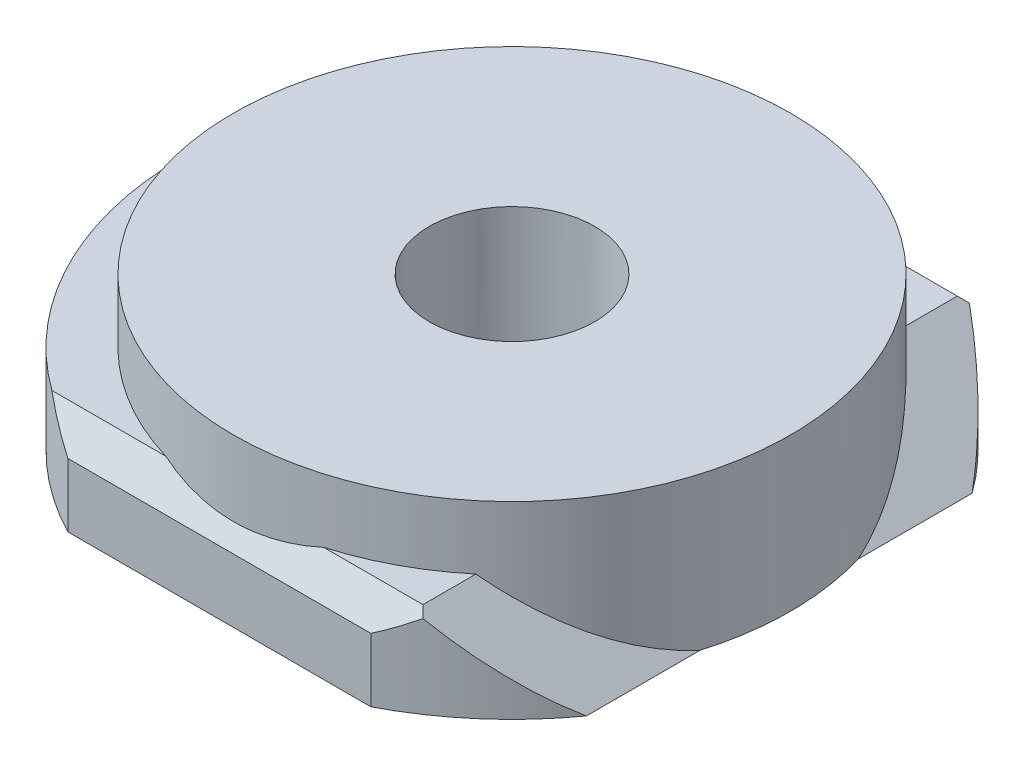
SolidWorks part; units mm, degrees
ref_plane "Front Plane" through (0, 0, 0) normal (0, 0, 1) x (1, 0, 0)
ref_plane "Top Plane" through (0, 0, 0) normal (0, 1, 0) x (1, 0, 0)
ref_plane "Right Plane" through (0, 0, 0) normal (1, 0, 0) x (0, 0, -1)
sketch "Sketch1" plane through (0, 0, 0) normal (0, 1, 0) x (1, 0, 0)
  circle A0 centre (0, 0) radius 6.05
  circle A1 centre (0, 0) radius 10.95
  dimension "D1" = 12.1
  dimension "D2" = 21.9
extrude "Boss-Extrude1" add sketch "Sketch1" against normal blind 2 contours A1 A0 | A0 | A0 | A1 region at (0, 0, 0) region at (-10.6403, 0, 0)
extrude "Boss-Extrude2" add sketch "Sketch1<3>" along normal blind 12
sketch "Sketch1<3>" plane through (0, 0, 0) normal (0, 1, 0) x (1, 0, 0) same geometry as "Sketch1"
sketch "Sketch2" plane through (0, 12, 0) normal (0, 1, 0) x (1, 0, 0)
  circle A0 centre (0, 0) radius 10.95
  circle A1 centre (0, 0) radius 12.95
  circle A2 centre (0, 0) radius 10.95 construction
  dimension "D1" = 2
extrude "Boss-Extrude3" add sketch "Sketch2" against normal up to surface (14 mm away) from offset 2.5 up to face at (0, -2, 10.95) offset against normal yes
sketch "Sketch3" plane through (0, 0, 0) normal (0, 1, 0) x (1, 0, 0)
  line L0 (-50, 11.5) -> (-50, 34.5)
  line L1 (-50, -11.5) -> (50, -11.5)
  line L2 (-50, -11.5) -> (-50, 11.5)
  line L3 (-50, 11.5) -> (50, 11.5)
  line L4 (50, -11.5) -> (50, 11.5)
  line L5 (-50, -11.5) -> (50, 11.5) construction
  line L6 (-50, 11.5) -> (50, -11.5) construction
  line L7 (-50, 11.5) -> (50, 11.5)
  line L8 (-50, 34.5) -> (50, 34.5)
  line L9 (50, 11.5) -> (50, 34.5)
  line L10 (50, -11.5) -> (-50, -11.5)
  line L11 (50, -11.5) -> (50, -34.5)
  line L12 (-50, -11.5) -> (-50, -34.5)
  line L13 (50, -34.5) -> (-50, -34.5)
  point P0 (0, 0)
  dimension "D1" = 23
  dimension "D2" = 100
extrude "Cut-Extrude1" cut sketch "Sketch3" against normal through all both and the other way through all contours L13 L11 L1 L12 | L3 L9 L8 L0 | L0 L7 L9 L8 region at (0, 0, -23) region at (0, 0, 23)
sketch "Sketch4" plane through (0, 0, 0) normal (0, 0, 1) x (1, 0, 0)
  line L0 (4.5, 12) -> (13, 3.5)
  line L1 (0, 0) -> (13, 0)
  line L2 (0, 0) -> (0, 12)
  line L3 (0, 12) -> (13, 12)
  line L4 (13, 0) -> (13, 12)
  line L5 (13, 3.5) -> (4.5, 3.5)
  line L6 (13, 3.5) -> (13, 12)
  line L7 (13, 12) -> (4.5, 12)
  line L8 (4.5, 3.5) -> (4.5, 12)
  dimension "D1" = 13
  dimension "D2" = 12
  dimension "D3" = 4.5
extrude "Cut-Extrude3" cut sketch "Sketch4" against normal through all both and the other way through all contours L0 L4 L3 region at (10.1667, 9.1667, 0)
extrude "Boss-Extrude4" add sketch "Sketch1<5>" along normal up to surface (12 mm away) up to face at (-2, 12, 0)
sketch "Sketch1<5>" plane through (0, 0, 0) normal (0, 1, 0) x (1, 0, 0) same geometry as "Sketch1"
chamfer "Chamfer1" distance 1 angle 45 2 edges at (0, 9.5, 11.5) (0, 9.5, -11.5)
sketch "Sketch7" plane through (0, 0, 0) normal (0, 1, 0) x (1, 0, 0)
  circle A1 centre (0, 0) radius 6.05
  circle A2 centre (0, 0) radius 6.05
  dimension "D1" = 0
extrude "Boss-Extrude5" add sketch "Sketch7" along normal up to surface (12 mm away) up to face at (0, 12, 10.95)
sketch "Sketch6" plane through (0, 0, 0) normal (0, 1, 0) x (1, 0, 0)
  circle A0 centre (0, 0) radius 3.25
  dimension "D1" = 6.5
extrude "Cut-Extrude5" cut sketch "Sketch6" against normal through all both and the other way through all
sketch "Sketch9" plane through (0, -2, 0) normal (0, -1, 0) x (1, 0, 0)
  line L2 (5.9542, 11.5) -> (-5.9542, 11.5)
  line L3 (-5.9542, -11.5) -> (5.9542, -11.5)
  line L4 (5.9542, 11.5) -> (-5.9542, 11.5)
  line L5 (-5.9542, -11.5) -> (5.9542, -11.5)
  arc A2 (-5.9542, 11.5) -> (-5.9542, -11.5) centre (0, 0) ccw
  arc A3 (5.9542, -11.5) -> (5.9542, 11.5) centre (0, 0) ccw
  arc A4 (-5.9542, 11.5) -> (-5.9542, -11.5) centre (0, 0) ccw
  arc A5 (5.9542, -11.5) -> (5.9542, 11.5) centre (0, 0) ccw
  dimension "D1" = 0
extrude "Cut-Extrude7" cut sketch "Sketch9" against normal blind 8
